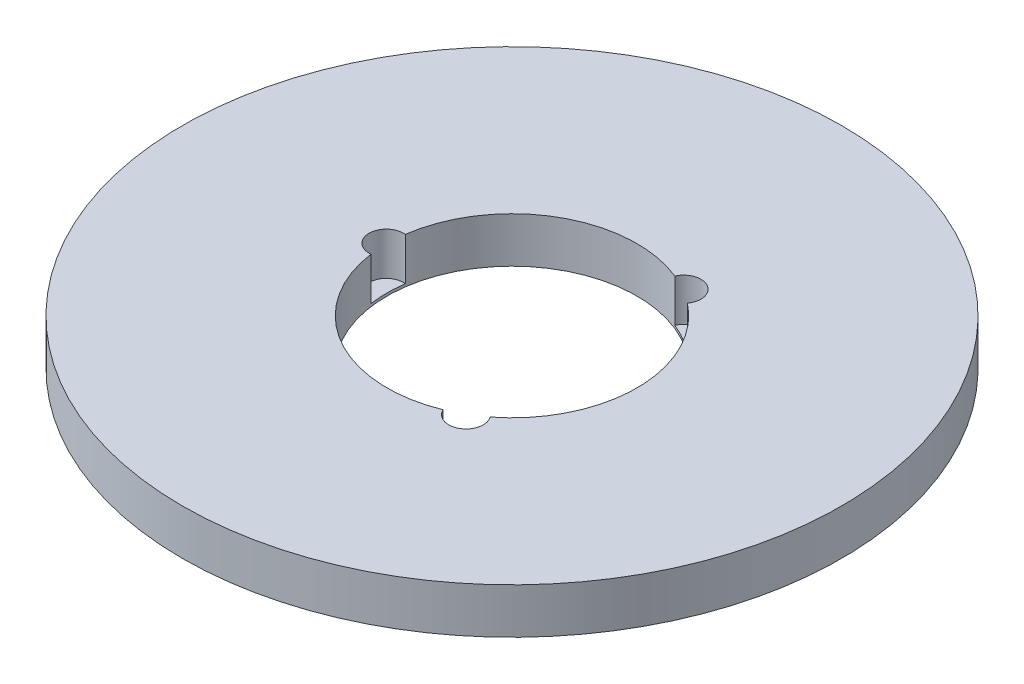
SolidWorks part; units mm, degrees
ref_plane "Front Plane" through (0, 0, 0) normal (0, 0, 1) x (1, 0, 0)
ref_plane "Top Plane" through (0, 0, 0) normal (0, 1, 0) x (1, 0, 0)
ref_plane "Right Plane" through (0, 0, 0) normal (1, 0, 0) x (0, 0, -1)
sketch "Sketch1" plane through (0, 0, 0) normal (0, 1, 0) x (1, 0, 0)
  circle A0 centre (0, 0) radius 72.5
  dimension "FLANGE_OD" = 145
extrude "Boss-Extrude1" add sketch "Sketch1" along normal blind 10
sketch "Sketch2" plane through (0, 0, 0) normal (0, 1, 0) x (1, 0, 0)
  circle A0 centre (0, 0) radius 27.5
  dimension "BORE_D" = 55
extrude "Cut-Extrude1" cut sketch "Sketch2" along normal through all
sketch "Sketch3" plane through (0, 10, 0) normal (0, 1, 0) x (1, 0, 0)
  circle A0 centre (0, 0) radius 27.6431 construction
  circle A1 centre (-27.6431, 0) radius 3.8021
  dimension "BOLT_D" = 7.6041
  dimension "BOLT_PCD" = 55.2861
extrude "Cut-Extrude2" cut sketch "Sketch3" against normal blind 9.3951
pattern_circular "CirPattern1" count 3 over 360 about axis through (0, 0, 0) along (0, 1, 0) of "Cut-Extrude2"
